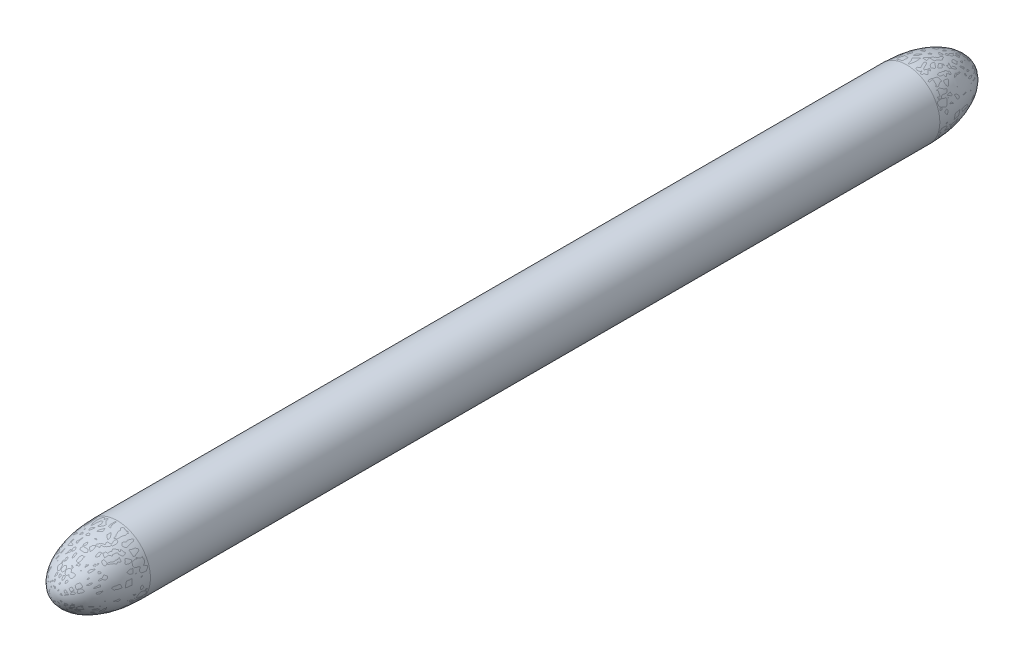
SolidWorks part; units mm, degrees
material "2024-T3"
ref_plane "Plano frontal" through (0, 0, 0) normal (0, 0, 1) x (1, 0, 0)
ref_plane "Plano superior" through (0, 0, 0) normal (0, 1, 0) x (1, 0, 0)
ref_plane "Plano direito" through (0, 0, 0) normal (1, 0, 0) x (0, 0, -1)
sketch "Esboço1" plane through (0, 0, 0) normal (0, 0, 1) x (1, 0, 0)
  circle A0 centre (0, 0) radius 1050
  dimension "D1" = 2100
extrude "Ressalto-extrusão1" add sketch "Esboço1" along normal blind 25000
dome "Domo2" faces to dome 1 distance 2000 reverse direction no elliptical dome yes face at (1050, 0, 25000) parameters "D1"=2000
dome "Domo3" faces to dome 1 distance 2000 reverse direction no elliptical dome yes face at (1050, 0, 0) parameters "D1"=2000
shell "Casca1" thickness 3
